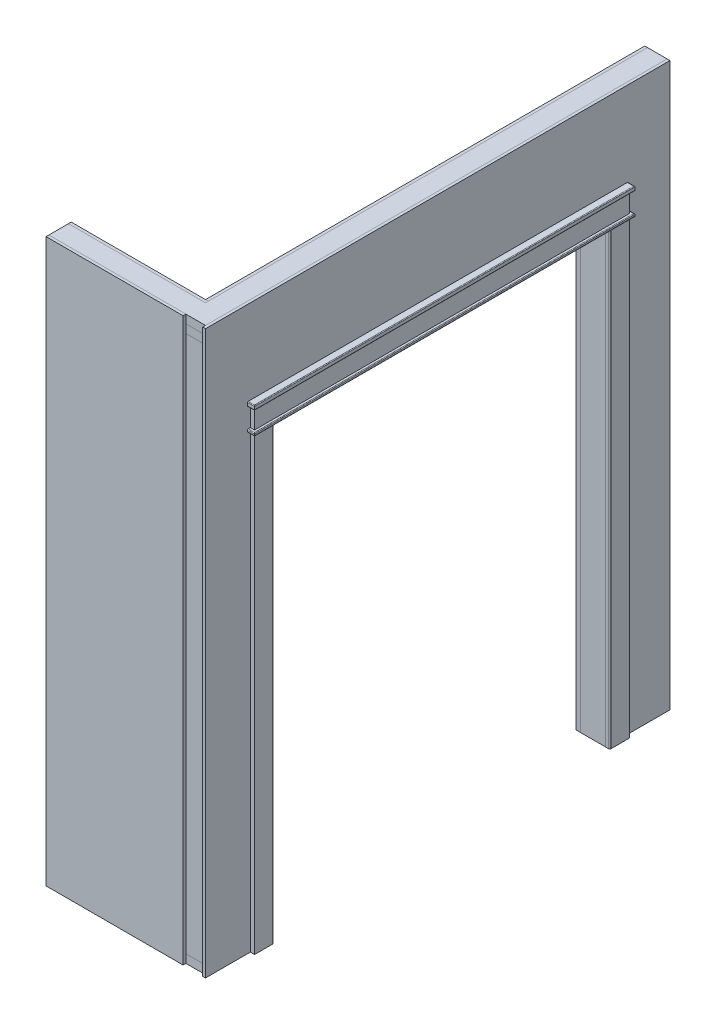
SolidWorks part; units mm, degrees
ref_plane "Front Plane" through (0, 0, 0) normal (0, 0, 1) x (1, 0, 0)
ref_plane "Top Plane" through (0, 0, 0) normal (0, 1, 0) x (1, 0, 0)
ref_plane "Right Plane" through (0, 0, 0) normal (1, 0, 0) x (0, 0, -1)
sketch "Sketch1" plane through (0, 0, 0) normal (0, 1, 0) x (1, 0, 0)
  line L1 (0, 0) -> (3581.4, 0)
  line L2 (0, 0) -> (0, 3479.8)
  line L3 (0, 3479.8) -> (3581.4, 3479.8)
  line L4 (3581.4, 0) -> (3581.4, 3479.8)
  line L9 (0, 76.2) -> (774.7, 76.2)
  line L10 (0, 1230.0171) -> (46.8505, 1230.0171)
  line L11 (0, 1230.0171) -> (0, 1143)
  line L12 (0, 1143) -> (46.8505, 1143)
  line L13 (46.8505, 1230.0171) -> (46.8505, 1143)
  line L14 (0, 76.2) -> (12.7, 76.2)
  line L15 (0, 977.9) -> (12.7, 977.9)
  line L16 (0, 977.9) -> (0, 850.9)
  line L17 (0, 850.9) -> (12.7, 850.9)
  line L18 (12.7, 977.9) -> (12.7, 850.9)
  line L19 (0, 76.2) -> (0, 0)
  line L20 (0, 0) -> (12.7, 0)
  line L21 (12.7, 76.2) -> (12.7, 0)
  arc A0 (0, 848.6682) -> (774.7, 76.2) centre (1.1159, 75.0841) cw
  dimension "D1" = 3581.4
  dimension "D2" = 3479.8
  dimension "D8" = 774.7
  dimension "D9" = 12.7
  dimension "D10" = 76.2
  dimension "D11" = 0
  dimension "D12" = 2249.7829
sketch "Sketch2" plane through (0, 0, 0) normal (0, 1, 0) x (1, 0, 0)
  line L0 (0, 0) -> (0, 3479.8) construction
  line L1 (0, 1473.2) -> (622.3, 1473.2)
  line L2 (0, 1473.2) -> (0, 1384.3)
  line L3 (0, 1384.3) -> (622.3, 1384.3)
  line L4 (622.3, 1473.2) -> (622.3, 1384.3)
  line L5 (0, 3479.8) -> (3581.4, 3479.8) construction
  dimension "D1" = 622.3
  dimension "D2" = 88.9
  dimension "D3" = 2006.6
extrude "Sole Plate 1" add sketch "Sketch2" along normal blind 38.1
sketch "Sketch3" plane through (0, 0, 0) normal (0, 1, 0) x (1, 0, 0)
  line L0 (711.2, 330.372) -> (711.2, 50330.372) construction
  line L1 (711.2, 1384.3) -> (622.3, 1384.3)
  line L2 (711.2, 1384.3) -> (711.2, 1644.65)
  line L3 (711.2, 1644.65) -> (622.3, 1644.65)
  line L4 (622.3, 1384.3) -> (622.3, 1644.65)
  line L5 (-1000, 3479.8) -> (49000, 3479.8) construction
  line L6 (0, 0) -> (0, 3479.8) construction
  line L7 (711.2, 3479.8) -> (622.3, 3479.8)
  line L8 (711.2, 3479.8) -> (711.2, 3206.75)
  line L9 (711.2, 3206.75) -> (622.3, 3206.75)
  line L10 (622.3, 3479.8) -> (622.3, 3206.75)
  line L12 (622.3, 1473.2) -> (0, 1473.2) construction
  dimension "D1" = 88.9
  dimension "D2" = 260.35
  dimension "D3" = 273.05
  dimension "D4" = 0
  dimension "D5" = 88.9
  dimension "D6" = 711.2
  dimension "D7" = 1562.1
  dimension "D8" = 2006.6
extrude "Sole Plate 2" add sketch "Sketch3" along normal blind 38.1 separate body
sketch "Sketch5" plane through (0, 38.1, 0) normal (0, 1, 0) x (1, 0, 0)
  line L1 (711.2, 1384.3) -> (622.3, 1384.3)
  line L2 (711.2, 1384.3) -> (711.2, 1422.4)
  line L3 (711.2, 1422.4) -> (622.3, 1422.4)
  line L4 (622.3, 1384.3) -> (622.3, 1422.4)
  line L5 (622.3, 1460.5) -> (711.2, 1460.5)
  line L6 (622.3, 1460.5) -> (622.3, 1498.6)
  line L7 (622.3, 1498.6) -> (711.2, 1498.6)
  line L8 (711.2, 1460.5) -> (711.2, 1498.6)
  line L9 (711.2, 1644.65) -> (622.3, 1644.65) construction
  line L10 (711.2, 1384.3) -> (711.2, 1644.65) construction
  line L14 (0, 1384.3) -> (622.3, 1384.3) construction
  line L15 (622.3, 1473.2) -> (0, 1473.2) construction
  line L16 (0, 1473.2) -> (38.1, 1473.2)
  line L17 (0, 1473.2) -> (0, 1384.3)
  line L18 (0, 1384.3) -> (38.1, 1384.3)
  line L19 (38.1, 1473.2) -> (38.1, 1384.3)
  line L20 (406.4, 1473.2) -> (444.5, 1473.2)
  line L21 (406.4, 1473.2) -> (406.4, 1384.3)
  line L22 (406.4, 1384.3) -> (444.5, 1384.3)
  line L23 (444.5, 1473.2) -> (444.5, 1384.3)
  line L24 (622.3, 1644.65) -> (622.3, 1384.3) construction
  line L25 (711.2, 3206.75) -> (711.2, 3479.8) construction
  line L26 (622.3, 3479.8) -> (711.2, 3479.8)
  line L27 (622.3, 3479.8) -> (622.3, 3441.7)
  line L28 (622.3, 3441.7) -> (711.2, 3441.7)
  line L29 (711.2, 3479.8) -> (711.2, 3441.7)
  line L30 (711.2, 1606.55) -> (622.3, 1606.55)
  line L31 (711.2, 1606.55) -> (711.2, 1568.45)
  line L32 (711.2, 1568.45) -> (622.3, 1568.45)
  line L33 (622.3, 1606.55) -> (622.3, 1568.45)
  line L34 (622.3, 3479.8) -> (622.3, 3206.75) construction
  line L35 (622.3, 3282.95) -> (711.2, 3282.95)
  line L36 (622.3, 3282.95) -> (622.3, 3244.85)
  line L37 (622.3, 3244.85) -> (711.2, 3244.85)
  line L38 (711.2, 3282.95) -> (711.2, 3244.85)
  line L39 (622.3, 3206.75) -> (711.2, 3206.75) construction
  dimension "D1" = 88.9
  dimension "D2" = 38.1
  dimension "D3" = 88.9
  dimension "D4" = 38.1
  dimension "D5" = 38.1
  dimension "D6" = 38.1
  dimension "D7" = 38.1
  dimension "D8" = 406.4
  dimension "D9" = 38.1
  dimension "D10" = 38.1
  dimension "D11" = 38.1
  dimension "D12" = 38.1
  dimension "D13" = 76.2
extrude "Framing Studs" add sketch "Sketch5" along normal blind 2438.4 separate body
sketch "Sketch6" plane through (0, 38.1, 0) normal (0, 1, 0) x (1, 0, 0)
  line L1 (622.3, 3244.85) -> (711.2, 3244.85)
  line L2 (622.3, 3244.85) -> (622.3, 3206.75)
  line L3 (622.3, 3206.75) -> (711.2, 3206.75)
  line L4 (711.2, 3244.85) -> (711.2, 3206.75)
  line L5 (622.3, 1644.65) -> (711.2, 1644.65)
  line L6 (622.3, 1644.65) -> (622.3, 1606.55)
  line L7 (622.3, 1606.55) -> (711.2, 1606.55)
  line L8 (711.2, 1644.65) -> (711.2, 1606.55)
extrude "Jack Studs" add sketch "Sketch6" along normal blind 2030.4125 separate body
sketch "Sketch7" plane through (0, 2068.5125, 0) normal (0, 1, 0) x (1, 0, 0)
  line L0 (622.3, 1606.55) -> (711.2, 1606.55) construction
  line L1 (622.3, 1606.55) -> (711.2, 1606.55)
  line L2 (622.3, 1606.55) -> (622.3, 3244.85)
  line L3 (622.3, 3244.85) -> (711.2, 3244.85)
  line L4 (711.2, 1606.55) -> (711.2, 3244.85)
  dimension "D1" = 0
extrude "Header" add sketch "Sketch7" along normal blind 38.1 separate body
sketch "Sketch8" plane through (0, 2106.6125, 0) normal (0, 1, 0) x (1, 0, 0)
  line L1 (622.3, 1606.55) -> (711.2, 1606.55)
  line L2 (622.3, 1606.55) -> (622.3, 1644.65)
  line L3 (622.3, 1644.65) -> (711.2, 1644.65)
  line L4 (711.2, 1606.55) -> (711.2, 1644.65)
  line L5 (622.3, 2012.95) -> (711.2, 2012.95)
  line L6 (622.3, 3244.85) -> (711.2, 3244.85)
  line L7 (622.3, 3244.85) -> (622.3, 3206.75)
  line L8 (622.3, 3206.75) -> (711.2, 3206.75)
  line L9 (711.2, 3244.85) -> (711.2, 3206.75)
  line L10 (622.3, 2012.95) -> (622.3, 2051.05)
  line L11 (622.3, 2051.05) -> (711.2, 2051.05)
  line L12 (711.2, 2012.95) -> (711.2, 2051.05)
  line L13 (622.3, 2419.35) -> (711.2, 2419.35)
  line L14 (622.3, 2419.35) -> (622.3, 2457.45)
  line L15 (622.3, 2457.45) -> (711.2, 2457.45)
  line L16 (711.2, 2419.35) -> (711.2, 2457.45)
  line L17 (622.3, 2825.75) -> (711.2, 2825.75)
  line L18 (622.3, 2825.75) -> (622.3, 2863.85)
  line L19 (622.3, 2863.85) -> (711.2, 2863.85)
  line L20 (711.2, 2825.75) -> (711.2, 2863.85)
  dimension "D1" = 38.1
  dimension "D2" = 38.1
  dimension "D3" = 4
extrude "Cripple Studs" add sketch "Sketch8" along normal up to surface (369.8875 mm away) separate body up to face at (666.75, 2476.5, -3263.9)
sketch "Sketch9" plane through (0, 2476.5, 0) normal (0, 1, 0) x (1, 0, 0)
  line L1 (622.3, 1473.2) -> (0, 1473.2)
  line L2 (622.3, 1473.2) -> (622.3, 1384.3)
  line L3 (622.3, 1384.3) -> (0, 1384.3)
  line L4 (0, 1473.2) -> (0, 1384.3)
  line L5 (711.2, 1384.3) -> (622.3, 1384.3)
  line L6 (711.2, 1384.3) -> (711.2, 3479.8)
  line L7 (711.2, 3479.8) -> (622.3, 3479.8)
  line L8 (622.3, 1384.3) -> (622.3, 3479.8)
  line M14 (711.2, 1384.3) -> (711.2, 1422.4)
  line M15 (711.2, 1422.4) -> (622.3, 1422.4)
  line M16 (622.3, 1422.4) -> (622.3, 1384.3)
  line M17 (622.3, 1384.3) -> (711.2, 1384.3)
extrude "Top Plate 1" add sketch "Sketch9" along normal blind 38.1 separate body contours L3 L2 L1 | L8 L2 L5 L6 L7 | M17 M14 M15 M16 region at (311.15, 2476.5, -1428.75) region at (666.75, 2476.5, -2451.1) region at (666.75, 2476.5, -1403.35)
sketch "Sketch10" plane through (0, 0, -1473.2) normal (0, 0, -1) x (-1, 0, 0)
  line L1 (0, 2552.7) -> (-622.3, 2552.7)
  line L2 (0, 2552.7) -> (0, 0)
  line L3 (0, 0) -> (-622.3, 0)
  line L4 (-622.3, 2552.7) -> (-622.3, 0)
  point P9 (13.0094, 2472.114)
  point P10 (168.4699, 2542.0387)
extrude "Inside Side Wall Dry Wall" add sketch "Sketch10" along normal blind 12.7 separate body
sketch "Sketch11" plane through (622.3, 0, 0) normal (-1, 0, 0) x (0, 0, 1)
  line L0 (-1485.9, 0) -> (-1485.9, 2552.7)
  line L1 (-1485.9, 2552.7) -> (-3479.8, 2552.7)
  line L2 (-3479.8, 2552.7) -> (-3479.8, 0)
  line L3 (-3479.8, 0) -> (-3206.75, 0)
  line L4 (-3206.75, 0) -> (-3206.75, 2068.5125)
  line L5 (-3206.75, 2068.5125) -> (-1644.65, 2068.5125)
  line L6 (-1644.65, 2068.5125) -> (-1644.65, 0)
  line L7 (-1644.65, 0) -> (-1485.9, 0)
  line L8 (-1473.2, 2514.6) -> (-3479.8, 2514.6) construction
  dimension "D1" = 38.1
extrude "Inside Main Wall Dry Wall" add sketch "Sketch11" along normal blind 12.7 separate body
sketch "Sketch12" plane through (0, 0, -1384.3) normal (0, 0, 1) x (1, 0, 0)
  line L1 (0, 2552.7) -> (622.3, 2552.7)
  line L2 (0, 2552.7) -> (0, 0)
  line L3 (0, 0) -> (622.3, 0)
  line L4 (622.3, 2552.7) -> (622.3, 0)
extrude "Outside Side Wall Dry Wall" add sketch "Sketch12" along normal blind 12.7 separate body
sketch "Sketch13" plane through (711.2, 0, 0) normal (1, 0, 0) x (0, 0, -1)
  line L0 (3479.8, 0) -> (3206.75, 0)
  line L1 (3206.75, 0) -> (3206.75, 2068.5125)
  line L2 (3206.75, 2068.5125) -> (1644.65, 2068.5125)
  line L3 (1644.65, 2068.5125) -> (1644.65, 0)
  line L4 (1644.65, 0) -> (1371.6, 0)
  line L5 (1371.6, 0) -> (1371.6, 2552.7)
  line L6 (1371.6, 2552.7) -> (3479.8, 2552.7)
  line L7 (3479.8, 2552.7) -> (3479.8, 0)
  line L9 (1384.3, 2476.5) -> (3479.8, 2476.5) construction
  dimension "D1" = 76.2
extrude "Outside Main Wall Dry Wall" add sketch "Sketch13" along normal blind 12.7 separate body
sketch "Sketch21" plane through (0, 2514.6, 0) normal (0, 1, 0) x (1, 0, 0)
  line L0 (622.3, 3479.8) -> (622.3, 1473.2)
  line L1 (622.3, 1473.2) -> (0, 1473.2)
  line L2 (0, 1473.2) -> (0, 1384.3)
  line L3 (0, 1384.3) -> (711.2, 1384.3)
  line L4 (711.2, 1384.3) -> (711.2, 3479.8)
  line L5 (711.2, 3479.8) -> (622.3, 3479.8)
extrude "Top Plate 2" add sketch "Sketch21" along normal blind 38.1 separate body
sketch "Sketch14" plane through (723.9, 0, 0) normal (1, 0, 0) x (0, 0, -1)
  line L0 (1644.65, 2068.5125) -> (3206.75, 2068.5125) construction
  line L1 (1663.7, 0) -> (1574.8, 0)
  line L2 (1663.7, 0) -> (1663.7, 2049.4625)
  line L3 (1663.7, 2049.4625) -> (1574.8, 2049.4625)
  line L4 (1574.8, 0) -> (1574.8, 2049.4625)
  line L5 (1562.1, 2062.1625) -> (3289.3, 2062.1625)
  line L6 (3187.7, 0) -> (3276.6, 0)
  line L7 (3187.7, 0) -> (3187.7, 2049.4625)
  line L8 (3187.7, 2049.4625) -> (3276.6, 2049.4625)
  line L9 (3276.6, 0) -> (3276.6, 2049.4625)
  line L10 (1574.8, 2049.4625) -> (3289.3, 2049.4625)
  line L11 (1562.1, 2062.1625) -> (1562.1, 2049.4625)
  line L12 (3289.3, 2049.4625) -> (1562.1, 2049.4625)
  line L13 (3289.3, 2049.4625) -> (3289.3, 2062.1625)
  line L14 (1574.8, 2062.1625) -> (3276.6, 2062.1625)
  line L15 (1574.8, 2062.1625) -> (1574.8, 2151.0625)
  line L16 (1574.8, 2151.0625) -> (3276.6, 2151.0625)
  line L17 (3276.6, 2062.1625) -> (3276.6, 2151.0625)
  line L18 (1562.1, 2170.1125) -> (3289.3, 2170.1125)
  line L19 (1562.1, 2170.1125) -> (1562.1, 2151.0625)
  line L20 (1562.1, 2151.0625) -> (3289.3, 2151.0625)
  line L21 (3289.3, 2170.1125) -> (3289.3, 2151.0625)
  line L22 (1562.1, 2049.4625) -> (1574.8, 2049.4625)
  line M4 (1371.6, 0) -> (1644.65, 0)
  line M5 (1644.65, 0) -> (1644.65, 2068.5125)
  line M6 (1644.65, 2068.5125) -> (3206.75, 2068.5125)
  line M7 (3206.75, 2068.5125) -> (3206.75, 0)
  line M8 (3206.75, 0) -> (3479.8, 0)
  dimension "D2" = 88.9
  dimension "D3" = 88.9
  dimension "D4" = 0
  dimension "D5" = 12.7
  dimension "D8" = 88.9
  dimension "D9" = 19.05
  dimension "D10" = 19.05
  dimension "D11" = 0
  dimension "D12" = 0
  dimension "D13" = 12.7
  dimension "D16" = 0
  dimension "D17" = 0
  dimension "D18" = 12.7
extrude "Casing Flat" add sketch "Sketch14" along normal blind 19.05 separate body contours L4 L3 M4 M5 | L17 L16 L15 | L9 L8 M8 M7 | M5 M7 M6 | L2 L3 L1 M5 | L8 L7 L6 M7 region at (723.9, 1024.7312, -1654.175) region at (723.9, 1024.7312, -1609.725) region at (723.9, 1024.7312, -3197.225) region at (723.9, 2065.3375, -2425.7) region at (723.9, 2109.5086, -2425.7) region at (723.9, 1024.7312, -3241.675)
extrude "Casing Fillet" add sketch "Sketch14<3>" along normal blind 31.75 contours L21 L18 L19 L20 L16 | L3 L10 L8 L5 M7 M5 | L12 L3 L5 L11 M5 | L10 L13 L5 L8 M7
sketch "Sketch14<3>" plane through (723.9, 0, 0) normal (1, 0, 0) x (0, 0, -1) same geometry as "Sketch14"
fillet "Fillet1" radius 3.175 12 edges at (739.775, 2170.1125, -1562.1) (739.775, 2151.0625, -1562.1) (755.65, 2170.1125, -2425.7) (755.65, 2151.0625, -2425.7) (739.775, 2170.1125, -3289.3) (739.775, 2151.0625, -3289.3) (739.775, 2049.4625, -3289.3) (739.775, 2049.4625, -1562.1) (755.65, 2049.4625, -2425.7) (739.775, 2062.1625, -3289.3) (755.65, 2062.1625, -2425.7) (739.775, 2062.1625, -1562.1)
fillet "Fillet2" radius 6.35 2 edges at (742.95, 1024.7312, -1663.7) (742.95, 1024.7312, -3187.7)
sketch "Sketch17" plane through (0, 2068.5125, 0) normal (0, -1, 0) x (-1, 0, 0)
  line L1 (-609.6, 1644.65) -> (-723.9, 1644.65)
  line L2 (-609.6, 1644.65) -> (-609.6, 3206.75)
  line L3 (-609.6, 3206.75) -> (-723.9, 3206.75)
  line L4 (-723.9, 1644.65) -> (-723.9, 3206.75)
  dimension "D1" = 114.3
extrude "Trim Door Top" add sketch "Sketch17" along normal blind 19.05 separate body
sketch "Sketch18" plane through (0, 0, -3206.75) normal (0, 0, 1) x (1, 0, 0)
  line L1 (609.6, 2049.4625) -> (723.9, 2049.4625)
  line L2 (609.6, 2049.4625) -> (609.6, 0)
  line L3 (609.6, 0) -> (723.9, 0)
  line L4 (723.9, 2049.4625) -> (723.9, 0)
extrude "Trim Door Right" add sketch "Sketch18" along normal blind 19.05 separate body
sketch "Sketch19" plane through (0, 0, -1644.65) normal (0, 0, -1) x (-1, 0, 0)
  line L1 (-723.9, 2049.4625) -> (-609.6, 2049.4625)
  line L2 (-723.9, 2049.4625) -> (-723.9, 0)
  line L3 (-723.9, 0) -> (-609.6, 0)
  line L4 (-609.6, 2049.4625) -> (-609.6, 0)
extrude "Trim Door Left" add sketch "Sketch19" along normal blind 19.05 separate body
sketch "Sketch20" plane through (609.6, 0, 0) normal (-1, 0, 0) x (0, 0, 1)
  line L1 (-1663.7, 0) -> (-1574.8, 0)
  line L2 (-1663.7, 0) -> (-1663.7, 2049.4625)
  line L3 (-1663.7, 2049.4625) -> (-1574.8, 2049.4625)
  line L4 (-1574.8, 0) -> (-1574.8, 2049.4625)
  line L5 (-3187.7, 0) -> (-3276.6, 0)
  line L6 (-3187.7, 0) -> (-3187.7, 2049.4625)
  line L7 (-3187.7, 2049.4625) -> (-3276.6, 2049.4625)
  line L8 (-3276.6, 0) -> (-3276.6, 2049.4625)
  line L9 (-3276.6, 2049.4625) -> (-1574.8, 2049.4625)
  line L10 (-3276.6, 2049.4625) -> (-3276.6, 2138.3625)
  line L11 (-3276.6, 2138.3625) -> (-1574.8, 2138.3625)
  line L12 (-1574.8, 2049.4625) -> (-1574.8, 2138.3625)
  line M6 (-3206.75, 0) -> (-3206.75, 2068.5125)
  line M7 (-3206.75, 2068.5125) -> (-1644.65, 2068.5125)
  line M8 (-1644.65, 2068.5125) -> (-1644.65, 0)
  dimension "D1" = 88.9
  dimension "D2" = 88.9
  dimension "D3" = 88.9
extrude "Casing Door interior Sides" add sketch "Sketch20" along normal blind 19.05 separate body contours L3 L2 L1 L4 | L7 L6 L5 L8
extrude "Casing Door Interior Top" add sketch "Sketch20<4>" along normal blind 19.05 separate body contours L3 L12 L11 L10 L7 M6 M7 M8 | L7 L9 L3 M8 M7 M6 region at (609.6, 2058.9875, -2425.7) region at (609.6, 2102.4641, -2425.7)
sketch "Sketch20<4>" plane through (609.6, 0, 0) normal (-1, 0, 0) x (0, 0, 1) same geometry as "Sketch20"
sketch "Sketch23" plane through (0, 38.1, 0) normal (0, 1, 0) x (1, 0, 0)
  line L0 (622.3, 1473.2) -> (0, 1473.2) construction
  line L1 (622.3, 1384.3) -> (584.2, 1384.3)
  line L2 (622.3, 1384.3) -> (622.3, 1473.2)
  line L3 (622.3, 1473.2) -> (584.2, 1473.2)
  line L4 (584.2, 1384.3) -> (584.2, 1473.2)
  dimension "D1" = 38.1
extrude "Boss-Extrude1" add sketch "Sketch23" along normal blind 2438.4 separate body
